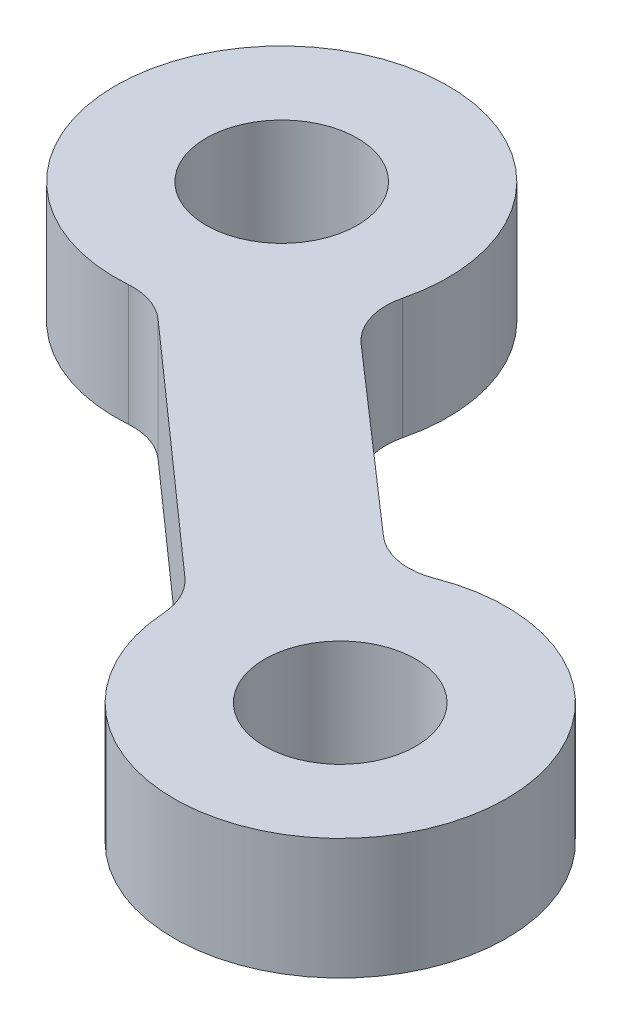
SolidWorks part; units mm, degrees
ref_plane "Front Plane" through (0, 0, 0) normal (0, 0, 1) x (1, 0, 0)
ref_plane "Top Plane" through (0, 0, 0) normal (0, 1, 0) x (1, 0, 0)
ref_plane "Right Plane" through (0, 0, 0) normal (1, 0, 0) x (0, 0, -1)
sketch "Sketch2" plane through (0, 0, 0) normal (0, 1, 0) x (1, 0, 0)
  line L7 (94.9551, 38.1723) -> (87.0277, 45.1049)
  line L12 (92.5032, 34.0063) -> (83.2947, 42.1711)
  line L13 (83.2947, 42.1711) -> (92.5032, 34.0063)
  line L18 (87.0277, 45.1049) -> (94.9551, 38.1723)
  arc A0 (87.0277, 45.1049) -> (83.2947, 42.1711) centre (82.0956, 47.5388) ccw
  circle A7 centre (82.0956, 47.5388) radius 2.5
  arc A10 (92.5032, 34.0063) -> (94.9551, 38.1723) centre (97.9869, 33.5834) ccw
  circle A17 centre (97.9869, 33.5834) radius 2.5
extrude "Boss-Extrude1" add sketch "Sketch2" along normal blind 4 contours L7 L13 L18 A7 A17 region at (89.8832, 0, -40.3741)
fillet "Fillet1" radius 2 4 edges at (83.2947, 2, -42.1711) (92.5032, 2, -34.0063) (87.0277, 2, -45.1049) (94.9551, 2, -38.1723)
